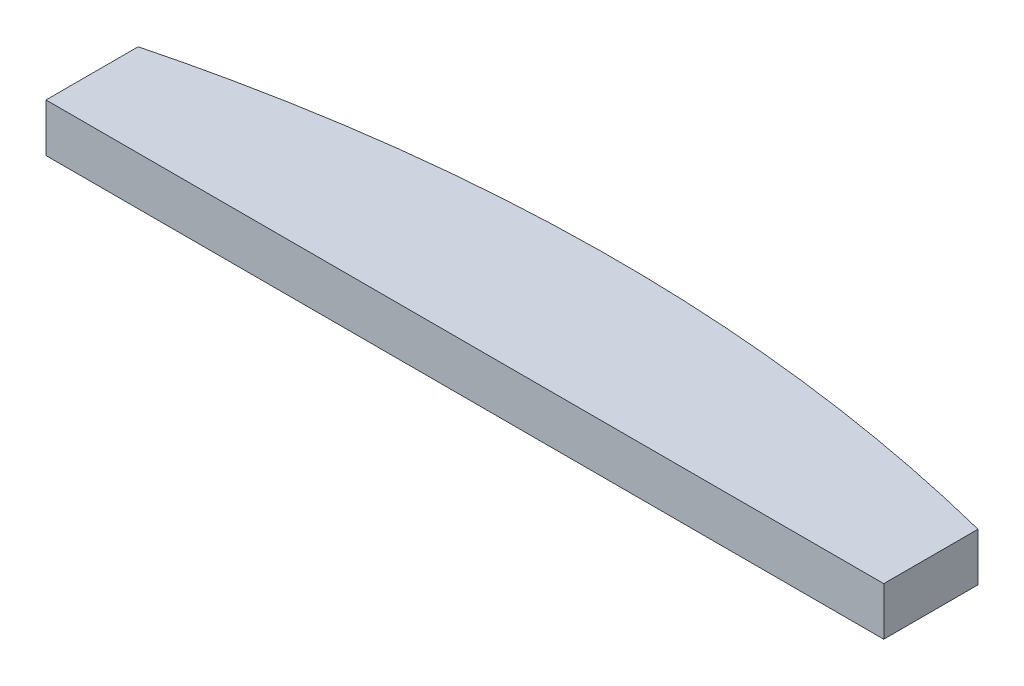
SolidWorks part; units mm, degrees
ref_plane "Front Plane" through (0, 0, 0) normal (0, 0, 1) x (1, 0, 0)
ref_plane "Top Plane" through (0, 0, 0) normal (0, 1, 0) x (1, 0, 0)
ref_plane "Right Plane" through (0, 0, 0) normal (1, 0, 0) x (0, 0, -1)
sketch "Sketch1" plane through (0, 0, 0) normal (0, 1, 0) x (1, 0, 0)
  line L1 (0, 0) -> (-304.8, 0)
  line L2 (0, 0) -> (0, 76.2)
  line L3 (0, 76.2) -> (-304.8, 76.2)
  line L4 (-304.8, 0) -> (-304.8, 76.2)
  dimension "D1" = 304.8
  dimension "D2" = 76.2
extrude "Boss-Extrude1" add sketch "Sketch1" along normal blind 3.175
sketch "Sketch2" plane through (0, 3.175, 0) normal (0, 1, 0) x (1, 0, 0)
  line L0 (-304.8, 76.2) -> (-304.8, 0) construction
  line L1 (-304.8, 6.35) -> (-215.9, 6.35) construction
  line L2 (-304.8, 6.35) -> (-304.8, 0) construction
  line L3 (-304.8, 0) -> (-215.9, 0) construction
  line L4 (-215.9, 6.35) -> (-215.9, 0) construction
  line L5 (-304.8, 0) -> (0, 0) construction
  line L6 (-304.8, 6.35) -> (-311.15, 6.35) construction
  line L7 (-311.15, 6.35) -> (-311.15, 0) construction
  line L8 (-311.15, 0) -> (-304.8, 0) construction
  line L9 (-215.9, 6.35) -> (-209.55, 6.35) construction
  line L10 (-209.55, 6.35) -> (-209.55, 0) construction
  line L11 (-209.55, 0) -> (-215.9, 0) construction
  line L12 (-304.8, 5.1324) -> (-304.8, 0.3904)
  line L13 (-215.9, 0.2103) -> (-215.9, 6.35)
  line L14 (-301.1367, 0) -> (-217.3799, 0)
  line L15 (-304.7482, 14.32) -> (-304.7482, 9.5781)
  line L16 (-215.8482, 9.3979) -> (-215.8482, 15.5376)
  line L17 (-301.0849, 9.1876) -> (-217.3281, 9.1876)
  line L18 (-304.7756, 23.4355) -> (-304.7756, 18.6936)
  line L19 (-215.8756, 18.5134) -> (-215.8756, 24.6532)
  line L20 (-301.1123, 18.3032) -> (-217.3555, 18.3032)
  line L21 (-304.7238, 32.6232) -> (-304.7238, 27.8813)
  line L22 (-215.8238, 27.7011) -> (-215.8238, 33.8408)
  line L23 (-301.0605, 27.4908) -> (-217.3037, 27.4908)
  line L24 (-304.6921, 41.752) -> (-304.6921, 37.0101)
  line L25 (-215.7921, 36.8299) -> (-215.7921, 42.9697)
  line L26 (-301.0288, 36.6197) -> (-217.272, 36.6197)
  line L27 (-304.6403, 50.9397) -> (-304.6403, 46.1977)
  line L28 (-215.7403, 46.0176) -> (-215.7403, 52.1573)
  line L29 (-300.977, 45.8073) -> (-217.2202, 45.8073)
  line L30 (-304.6677, 60.0552) -> (-304.6677, 55.3133)
  line L31 (-215.7677, 55.1331) -> (-215.7677, 61.2729)
  line L32 (-301.0044, 54.9229) -> (-217.2476, 54.9229)
  line L33 (-304.6159, 69.2428) -> (-304.6159, 64.5009)
  line L34 (-215.7159, 64.3207) -> (-215.7159, 70.4605)
  line L35 (-300.9526, 64.1105) -> (-217.1958, 64.1105)
  line L36 (-215.1839, 5.3155) -> (-215.1839, 0.5736)
  line L37 (-126.2839, 0.3934) -> (-126.2839, 6.5331)
  line L38 (-211.5206, 0.1831) -> (-127.7637, 0.1831)
  line L39 (-215.1321, 14.5031) -> (-215.1321, 9.7612)
  line L40 (-126.2321, 9.581) -> (-126.2321, 15.7207)
  line L41 (-211.4688, 9.3707) -> (-127.7119, 9.3707)
  line L42 (-215.1595, 23.6187) -> (-215.1595, 18.8768)
  line L43 (-126.2595, 18.6966) -> (-126.2595, 24.8363)
  line L44 (-211.4962, 18.4863) -> (-127.7393, 18.4863)
  line L45 (-215.1077, 32.8063) -> (-215.1077, 28.0644)
  line L46 (-126.2077, 27.8842) -> (-126.2077, 34.0239)
  line L47 (-211.4444, 27.6739) -> (-127.6875, 27.6739)
  spline S0 degree 3 poles (-304.8, 5.1324) (-295.0561, 7.9134) (-284.6351, 9.1758) (-256.6545, 7.9107) (-231.9837, 8.0391) (-215.9, 6.35) knots 0.033342 0.033342 0.033342 0.033342 0.196819 0.285044 0.915588 0.915588 0.915588 0.915588
  spline S1 degree 3 poles (-304.8, 0.3904) (-303.8212, 0.2292) (-302.6326, 0.1002) (-301.1367, 0) knots 0.767988 0.767988 0.767988 0.767988 1 1 1 1
  spline S2 degree 2 poles (-215.9, 0.2103) (-216.6026, 0.0759) (-217.3799, 0) knots 0.882957 0.882957 0.882957 1 1 1
  spline S3 degree 3 poles (-304.7482, 14.32) (-295.0043, 17.101) (-284.5833, 18.3634) (-256.6027, 17.0983) (-231.9319, 17.2267) (-215.8482, 15.5376) knots 0.033342 0.033342 0.033342 0.033342 0.196819 0.285044 0.915588 0.915588 0.915588 0.915588
  spline S4 degree 3 poles (-304.7482, 9.5781) (-303.7694, 9.4169) (-302.5808, 9.2879) (-301.0849, 9.1876) knots 0.767988 0.767988 0.767988 0.767988 1 1 1 1
  spline S5 degree 2 poles (-215.8482, 9.3979) (-216.5508, 9.2635) (-217.3281, 9.1876) knots 0.882957 0.882957 0.882957 1 1 1
  spline S6 degree 3 poles (-304.7756, 23.4355) (-295.0317, 26.2166) (-284.6108, 27.479) (-256.6301, 26.2139) (-231.9593, 26.3423) (-215.8756, 24.6532) knots 0.033342 0.033342 0.033342 0.033342 0.196819 0.285044 0.915588 0.915588 0.915588 0.915588
  spline S7 degree 3 poles (-304.7756, 18.6936) (-303.7969, 18.5324) (-302.6082, 18.4034) (-301.1123, 18.3032) knots 0.767988 0.767988 0.767988 0.767988 1 1 1 1
  spline S8 degree 2 poles (-215.8756, 18.5134) (-216.5782, 18.3791) (-217.3555, 18.3032) knots 0.882957 0.882957 0.882957 1 1 1
  spline S9 degree 3 poles (-304.7238, 32.6232) (-294.9799, 35.4042) (-284.5589, 36.6666) (-256.5783, 35.4015) (-231.9075, 35.5299) (-215.8238, 33.8408) knots 0.033342 0.033342 0.033342 0.033342 0.196819 0.285044 0.915588 0.915588 0.915588 0.915588
  spline S10 degree 3 poles (-304.7238, 27.8813) (-303.745, 27.72) (-302.5564, 27.591) (-301.0605, 27.4908) knots 0.767988 0.767988 0.767988 0.767988 1 1 1 1
  spline S11 degree 2 poles (-215.8238, 27.7011) (-216.5264, 27.5667) (-217.3037, 27.4908) knots 0.882957 0.882957 0.882957 1 1 1
  spline S12 degree 3 poles (-304.6921, 41.752) (-294.9482, 44.5331) (-284.5273, 45.7954) (-256.5466, 44.5304) (-231.8758, 44.6587) (-215.7921, 42.9697) knots 0.033342 0.033342 0.033342 0.033342 0.196819 0.285044 0.915588 0.915588 0.915588 0.915588
  spline S13 degree 3 poles (-304.6921, 37.0101) (-303.7134, 36.8489) (-302.5247, 36.7199) (-301.0288, 36.6197) knots 0.767988 0.767988 0.767988 0.767988 1 1 1 1
  spline S14 degree 2 poles (-215.7921, 36.8299) (-216.4947, 36.6956) (-217.272, 36.6197) knots 0.882957 0.882957 0.882957 1 1 1
  spline S15 degree 3 poles (-304.6403, 50.9397) (-294.8964, 53.7207) (-284.4755, 54.9831) (-256.4948, 53.718) (-231.824, 53.8464) (-215.7403, 52.1573) knots 0.033342 0.033342 0.033342 0.033342 0.196819 0.285044 0.915588 0.915588 0.915588 0.915588
  spline S16 degree 3 poles (-304.6403, 46.1977) (-303.6616, 46.0365) (-302.4729, 45.9075) (-300.977, 45.8073) knots 0.767988 0.767988 0.767988 0.767988 1 1 1 1
  spline S17 degree 2 poles (-215.7403, 46.0176) (-216.4429, 45.8832) (-217.2202, 45.8073) knots 0.882957 0.882957 0.882957 1 1 1
  spline S18 degree 3 poles (-304.6677, 60.0552) (-294.9238, 62.8363) (-284.5029, 64.0986) (-256.5222, 62.8336) (-231.8514, 62.9619) (-215.7677, 61.2729) knots 0.033342 0.033342 0.033342 0.033342 0.196819 0.285044 0.915588 0.915588 0.915588 0.915588
  spline S19 degree 3 poles (-304.6677, 55.3133) (-303.689, 55.1521) (-302.5003, 55.0231) (-301.0044, 54.9229) knots 0.767988 0.767988 0.767988 0.767988 1 1 1 1
  spline S20 degree 2 poles (-215.7677, 55.1331) (-216.4703, 54.9988) (-217.2476, 54.9229) knots 0.882957 0.882957 0.882957 1 1 1
  spline S21 degree 3 poles (-304.6159, 69.2428) (-294.872, 72.0239) (-284.4511, 73.2863) (-256.4704, 72.0212) (-231.7996, 72.1496) (-215.7159, 70.4605) knots 0.033342 0.033342 0.033342 0.033342 0.196819 0.285044 0.915588 0.915588 0.915588 0.915588
  spline S22 degree 3 poles (-304.6159, 64.5009) (-303.6372, 64.3397) (-302.4485, 64.2107) (-300.9526, 64.1105) knots 0.767988 0.767988 0.767988 0.767988 1 1 1 1
  spline S23 degree 2 poles (-215.7159, 64.3207) (-216.4185, 64.1864) (-217.1958, 64.1105) knots 0.882957 0.882957 0.882957 1 1 1
  spline S24 degree 3 poles (-215.1839, 5.3155) (-205.4399, 8.0965) (-195.019, 9.3589) (-167.0384, 8.0938) (-142.3676, 8.2222) (-126.2839, 6.5331) knots 0.033342 0.033342 0.033342 0.033342 0.196819 0.285044 0.915588 0.915588 0.915588 0.915588
  spline S25 degree 3 poles (-215.1839, 0.5736) (-214.2051, 0.4124) (-213.0165, 0.2834) (-211.5206, 0.1831) knots 0.767988 0.767988 0.767988 0.767988 1 1 1 1
  spline S26 degree 2 poles (-126.2839, 0.3934) (-126.9865, 0.2591) (-127.7637, 0.1831) knots 0.882957 0.882957 0.882957 1 1 1
  spline S27 degree 3 poles (-215.1321, 14.5031) (-205.3881, 17.2842) (-194.9672, 18.5465) (-166.9866, 17.2815) (-142.3158, 17.4098) (-126.2321, 15.7207) knots 0.033342 0.033342 0.033342 0.033342 0.196819 0.285044 0.915588 0.915588 0.915588 0.915588
  spline S28 degree 3 poles (-215.1321, 9.7612) (-214.1533, 9.6) (-212.9646, 9.471) (-211.4688, 9.3707) knots 0.767988 0.767988 0.767988 0.767988 1 1 1 1
  spline S29 degree 2 poles (-126.2321, 9.581) (-126.9347, 9.4467) (-127.7119, 9.3707) knots 0.882957 0.882957 0.882957 1 1 1
  spline S30 degree 3 poles (-215.1595, 23.6187) (-205.4155, 26.3997) (-194.9946, 27.6621) (-167.014, 26.397) (-142.3432, 26.5254) (-126.2595, 24.8363) knots 0.033342 0.033342 0.033342 0.033342 0.196819 0.285044 0.915588 0.915588 0.915588 0.915588
  spline S31 degree 3 poles (-215.1595, 18.8768) (-214.1807, 18.7155) (-212.9921, 18.5866) (-211.4962, 18.4863) knots 0.767988 0.767988 0.767988 0.767988 1 1 1 1
  spline S32 degree 2 poles (-126.2595, 18.6966) (-126.9621, 18.5622) (-127.7393, 18.4863) knots 0.882957 0.882957 0.882957 1 1 1
  spline S33 degree 3 poles (-215.1077, 32.8063) (-205.3637, 35.5874) (-194.9428, 36.8497) (-166.9622, 35.5847) (-142.2914, 35.713) (-126.2077, 34.0239) knots 0.033342 0.033342 0.033342 0.033342 0.196819 0.285044 0.915588 0.915588 0.915588 0.915588
  spline S34 degree 3 poles (-215.1077, 28.0644) (-214.1289, 27.9032) (-212.9403, 27.7742) (-211.4444, 27.6739) knots 0.767988 0.767988 0.767988 0.767988 1 1 1 1
  spline S35 degree 2 poles (-126.2077, 27.8842) (-126.9103, 27.7499) (-127.6875, 27.6739) knots 0.882957 0.882957 0.882957 1 1 1
  dimension "D1" = 88.9
  dimension "D2" = 6.35
  dimension "D3" = 6.35
  dimension "D4" = 6.35
  dimension "D5" = 2.54
  dimension "D6" = 30.48
extrude "Cut-Extrude3" cut sketch "Sketch2" against normal blind 0.254
sketch "Sketch3" plane through (0, 3.175, 0) normal (0, 1, 0) x (1, 0, 0)
  line L0 (-217.3799, 0) -> (0, 0) construction
  line L1 (-124.7737, 0) -> (-73.9737, 0)
  line L2 (-124.7737, 0) -> (-124.7737, 5.588)
  line L4 (-73.9737, 0) -> (-73.9737, 5.715)
  line L5 (-124.6661, 9.5552) -> (-73.8661, 9.5552)
  line L6 (-124.6661, 9.5552) -> (-124.6661, 15.1432)
  line L7 (-73.8661, 9.5552) -> (-73.8661, 15.2702)
  line L12 (-124.6047, 19.1295) -> (-73.8047, 19.1295)
  line L13 (-124.6047, 19.1295) -> (-124.6047, 24.7175)
  line L14 (-73.8047, 19.1295) -> (-73.8047, 24.8445)
  line L17 (-124.4952, 28.7633) -> (-73.6952, 28.7633)
  line L18 (-124.4952, 28.7633) -> (-124.4952, 34.3513)
  line L19 (-73.6952, 28.7633) -> (-73.6952, 34.4783)
  line L22 (-124.3858, 38.3971) -> (-73.5858, 38.3971)
  line L23 (-124.3858, 38.3971) -> (-124.3858, 43.9851)
  line L24 (-73.5858, 38.3971) -> (-73.5858, 44.1121)
  line L27 (-124.1668, 49.2351) -> (-73.3668, 49.2351)
  line L28 (-124.1668, 49.2351) -> (-124.1668, 54.8231)
  line L29 (-73.3668, 49.2351) -> (-73.3668, 54.9501)
  line L32 (-124.1389, 59.0137) -> (-73.3389, 59.0137)
  line L33 (-124.1389, 59.0137) -> (-124.1389, 64.6017)
  line L34 (-73.3389, 59.0137) -> (-73.3389, 64.7287)
  line L37 (-213.6694, 38.4491) -> (-162.8694, 38.4491)
  line L38 (-213.6694, 38.4491) -> (-213.6694, 44.0371)
  line L39 (-162.8694, 38.4491) -> (-162.8694, 44.1641)
  line L42 (-213.513, 49.2396) -> (-162.713, 49.2396)
  line L43 (-213.513, 49.2396) -> (-213.513, 54.8276)
  line L44 (-162.713, 49.2396) -> (-162.713, 54.9546)
  line L47 (-213.2002, 60.0302) -> (-162.4002, 60.0302)
  line L48 (-213.2002, 60.0302) -> (-213.2002, 65.6182)
  line L49 (-162.4002, 60.0302) -> (-162.4002, 65.7452)
  line L52 (0, 76.2) -> (-31.75, 76.2)
  line L53 (0, 76.2) -> (-304.8, 76.2) construction
  line L54 (-31.75, 76.2) -> (-63.5, 0)
  line L55 (-63.5, 0) -> (0, 0)
  line L56 (0, 0) -> (0, 76.2)
  spline S0 degree 2 poles (-124.7737, 5.588) (-99.3908, 12.6276) (-73.9737, 5.715) knots 0 0 0 1 1 1
  spline S1 degree 2 poles (-124.6661, 15.1432) (-99.282, 21.6837) (-73.8661, 15.2702) knots 0 0 0 1 1 1
  spline S2 degree 2 poles (-124.6047, 24.7175) (-99.2206, 31.2579) (-73.8047, 24.8445) knots 0 0 0 1 1 1
  spline S3 degree 2 poles (-124.4952, 34.3513) (-99.1112, 40.8917) (-73.6952, 34.4783) knots 0 0 0 1 1 1
  spline S4 degree 2 poles (-124.3858, 43.9851) (-99.0017, 50.5255) (-73.5858, 44.1121) knots 0 0 0 1 1 1
  spline S5 degree 2 poles (-124.1668, 54.8231) (-98.7827, 61.3635) (-73.3668, 54.9501) knots 0 0 0 1 1 1
  spline S6 degree 2 poles (-124.1389, 64.6017) (-98.7548, 71.1422) (-73.3389, 64.7287) knots 0 0 0 1 1 1
  spline S7 degree 2 poles (-213.6694, 44.0371) (-188.2853, 50.5775) (-162.8694, 44.1641) knots 0 0 0 1 1 1
  spline S8 degree 2 poles (-213.513, 54.8276) (-188.1289, 61.3681) (-162.713, 54.9546) knots 0 0 0 1 1 1
  spline S9 degree 2 poles (-213.2002, 65.6182) (-187.8162, 72.1587) (-162.4002, 65.7452) knots 0 0 0 1 1 1
  dimension "D1" = 5.588
  dimension "D2" = 5.715
  dimension "D3" = 5.588
  dimension "D4" = 5.715
  dimension "D5" = 5.588
  dimension "D6" = 5.715
  dimension "D7" = 5.588
  dimension "D8" = 5.715
  dimension "D9" = 5.588
  dimension "D10" = 5.715
  dimension "D11" = 5.588
  dimension "D12" = 5.715
  dimension "D13" = 5.588
  dimension "D14" = 5.715
  dimension "D15" = 5.588
  dimension "D16" = 5.715
  dimension "D17" = 5.588
  dimension "D18" = 5.715
  dimension "D19" = 5.588
  dimension "D20" = 5.715
  dimension "D21" = 31.75
  dimension "D22" = 63.5
extrude "Cut-Extrude5" cut sketch "Sketch3" against normal blind 0.254
extrude "Cut-Extrude8" cut sketch "Sketch3<2>" against normal through all flip side to cut contours S9 L48 L47 L49 region at (-187.7323, 3.175, -63.9952)
sketch "Sketch3<2>" plane through (0, 3.175, 0) normal (0, 1, 0) x (1, 0, 0) same geometry as "Sketch3"
